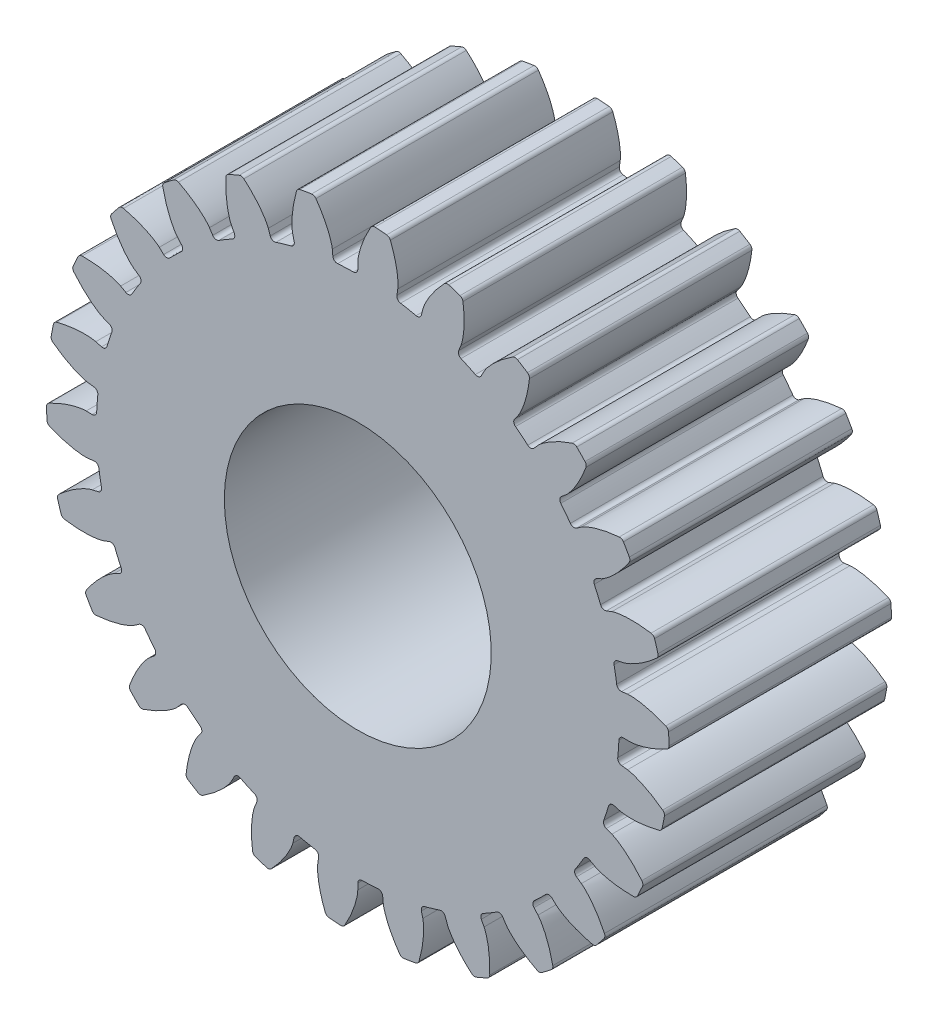
SolidWorks part; units mm, degrees
ref_plane "Front Plane" through (0, 0, 0) normal (0, 0, 1) x (1, 0, 0)
ref_plane "Top Plane" through (0, 0, 0) normal (0, 1, 0) x (1, 0, 0)
ref_plane "Right Plane" through (0, 0, 0) normal (1, 0, 0) x (0, 0, -1)
sketch "Involute Geometry" plane through (0, 0, 0) normal (0, 0, 1) x (1, 0, 0)
  line L0 (0, 12.216) -> (0, 0) construction
  line L1 (0, 0) -> (1.0333, 13.9618) construction
  line L2 (1.7984, 12.0829) -> (0, 0) construction
  line L3 (0.175, 12.9988) -> (0, 0) construction
  line L4 (0, 0) -> (1.7406, 12.883) construction
  circle A1 centre (0, 0) radius 12.216 construction
  circle A2 centre (0, 0) radius 13 construction
  circle A3 centre (0, 0) radius 14 construction
  circle A4 centre (0, 0) radius 11.75 construction
  arc A5 (0.6454, 13.9851) -> (1.4204, 13.9278) centre (0, 0) cw
  arc A6 (0.175, 12.9988) -> (1.7406, 12.883) centre (0, 0) cw construction
  spline S0 degree 4 poles (0, 12.216) (0, 12.2259) (0.0007, 12.2537) (0.0046, 12.3061) (0.0149, 12.3914) (0.0336, 12.4994) (0.064, 12.638) (0.108, 12.7997) (0.1647, 12.9755) (0.2354, 13.1642) (0.3138, 13.35) (0.3992, 13.5328) (0.4907, 13.7124) (0.6089, 13.9268) (0.7611, 14.1794) (0.9535, 14.4672) (1.1888, 14.7846) (1.4461, 15.0973) (1.7136, 15.3959) (1.9994, 15.6864) (2.287, 15.9594) (2.6008, 16.2305) (2.8982, 16.4744) (3.2472, 16.733) (3.5335, 16.9374) (3.9271, 17.1908) (4.1642, 17.3355) (4.4469, 17.4991) (4.5752, 17.5686) (4.654, 17.6115) knots 0 0 0 0 0 0.005377 0.015084 0.028532 0.04661 0.064855 0.092111 0.119476 0.146842 0.174209 0.201575 0.228941 0.256307 0.307035 0.361767 0.4165 0.471232 0.525964 0.580697 0.635429 0.690161 0.744894 0.799626 0.854358 0.909091 0.954545 1 1 1 1 1 construction
  spline S1 degree 4 poles (0, 12.216) (0, 12.2259) (0.0007, 12.2537) (0.0046, 12.3061) (0.0149, 12.3914) (0.0336, 12.4994) (0.064, 12.638) (0.108, 12.7997) (0.1647, 12.9755) (0.2354, 13.1642) (0.3138, 13.35) (0.3992, 13.5328) (0.4907, 13.7124) (0.6089, 13.9268) (0.7611, 14.1794) (0.9535, 14.4672) (1.1888, 14.7846) (1.4461, 15.0973) (1.7136, 15.3959) (1.9994, 15.6864) (2.287, 15.9594) (2.6008, 16.2305) (2.8982, 16.4744) (3.2472, 16.733) (3.5335, 16.9374) (3.8418, 17.1359) (3.9936, 17.2306) (4.0719, 17.2782) knots 0 0 0 0 0 0.005377 0.015084 0.028532 0.04661 0.064855 0.092111 0.119476 0.146842 0.174209 0.201575 0.228941 0.256307 0.307035 0.361767 0.4165 0.471232 0.525964 0.580697 0.635429 0.690161 0.744894 0.799626 0.854358 0.909091 0.909091 0.909091 0.909091 0.909091
  spline S3 degree 4 poles (1.7984, 12.0829) (1.7999, 12.0927) (1.8033, 12.1203) (1.8071, 12.1727) (1.8095, 12.2586) (1.8069, 12.3682) (1.7972, 12.5097) (1.7775, 12.6762) (1.7473, 12.8584) (1.7051, 13.0554) (1.655, 13.2507) (1.5974, 13.4441) (1.5334, 13.6352) (1.448, 13.8647) (1.3347, 14.1369) (1.1867, 14.45) (1.0007, 14.7985) (0.7922, 15.1457) (0.5716, 15.4804) (0.3317, 15.8098) (0.0874, 16.1222) (-0.1831, 16.4365) (-0.4413, 16.7215) (-0.7484, 17.0287) (-1.0015, 17.2731) (-1.3535, 17.5817) (-1.5667, 17.7597) (-1.8223, 17.9631) (-1.9389, 18.0507) (-2.0106, 18.1047) knots 0 0 0 0 0 0.005377 0.015084 0.028532 0.04661 0.064855 0.092111 0.119476 0.146842 0.174209 0.201575 0.228941 0.256307 0.307035 0.361767 0.4165 0.471232 0.525964 0.580697 0.635429 0.690161 0.744894 0.799626 0.854358 0.909091 0.954545 1 1 1 1 1 construction
  spline S4 degree 4 poles (1.7984, 12.0829) (1.7999, 12.0927) (1.8033, 12.1203) (1.8071, 12.1727) (1.8095, 12.2586) (1.8069, 12.3682) (1.7972, 12.5097) (1.7775, 12.6762) (1.7473, 12.8584) (1.7051, 13.0554) (1.655, 13.2507) (1.5974, 13.4441) (1.5334, 13.6352) (1.448, 13.8647) (1.3347, 14.1369) (1.1867, 14.45) (1.0007, 14.7985) (0.7922, 15.1457) (0.5716, 15.4804) (0.3317, 15.8098) (0.0874, 16.1222) (-0.1831, 16.4365) (-0.4413, 16.7215) (-0.7484, 17.0287) (-1.0015, 17.2731) (-1.2772, 17.5148) (-1.4134, 17.6308) (-1.4839, 17.6894) knots 0 0 0 0 0 0.005377 0.015084 0.028532 0.04661 0.064855 0.092111 0.119476 0.146842 0.174209 0.201575 0.228941 0.256307 0.307035 0.361767 0.4165 0.471232 0.525964 0.580697 0.635429 0.690161 0.744894 0.799626 0.854358 0.909091 0.909091 0.909091 0.909091 0.909091
  dimension "D5" = 6.923
sketch "Sketch2" plane through (0, 0, 0) normal (0, 0, 1) x (1, 0, 0)
  circle A0 centre (0, 0) radius 11.75 construction
  circle A1 centre (0, 0) radius 11.75
extrude "Boss-Extrude1" add sketch "Sketch2" along normal mid plane 10
sketch "Sketch3" plane through (0, 0, 0) normal (0, 0, 1) x (1, 0, 0)
  line L0 (0, 12.216) -> (0, 0) construction
  line L1 (1.7984, 12.0829) -> (0, 0) construction
  line L2 (0, 12.216) -> (0, 11.75)
  line L4 (1.7984, 12.0829) -> (1.7298, 11.622)
  circle A1 centre (0, 0) radius 11.75 construction
  arc A3 (0, 11.75) -> (1.7298, 11.622) centre (0, 0) cw
  arc A4 (1.4204, 13.9278) -> (0.6454, 13.9851) centre (0, 0) ccw construction
  arc A5 (1.4204, 13.9278) -> (0.6454, 13.9851) centre (0, 0) ccw
  spline S0 degree 4 poles (999.8581, 25.2356) (18.0155, 10.2173) (0.3577, 10.7107) (-0.0848, 11.5636) (0.0149, 12.3914) (0.0336, 12.4994) (0.064, 12.638) (0.108, 12.7997) (0.1647, 12.9755) (0.2354, 13.1642) (0.3138, 13.35) (0.3992, 13.5328) (0.4907, 13.7124) (0.6089, 13.9268) (0.7611, 14.1794) (0.9535, 14.4672) (1.1888, 14.7846) (1.4461, 15.0973) (1.7136, 15.3959) (1.9994, 15.6864) (2.287, 15.9594) (2.6008, 16.2305) (2.8982, 16.4744) (3.2472, 16.733) (4.4419, 17.5861) (8.1221, 19.6216) (-23.9178, -0.2396) (859.2438, 535.5339) knots -0.405932 -0.405932 -0.405932 -0.405932 -0.405932 0.005377 0.015084 0.028532 0.04661 0.064855 0.092111 0.119476 0.146842 0.174209 0.201575 0.228941 0.256307 0.307035 0.361767 0.4165 0.471232 0.525964 0.580697 0.635429 0.690161 0.744894 0.799626 0.854358 1.603617 1.603617 1.603617 1.603617 1.603617 only from (0, 12.216) to (3.8711, 11.595) construction
  spline S1 degree 4 poles (0, 12.216) (0, 12.2259) (0.0007, 12.2537) (0.0046, 12.3061) (0.0149, 12.3914) (0.0336, 12.4994) (0.064, 12.638) (0.108, 12.7997) (0.1647, 12.9755) (0.2354, 13.1642) (0.3138, 13.35) (0.3992, 13.5328) (0.4919, 13.7149) (0.5664, 13.8498) (0.6183, 13.9394) (0.6454, 13.9851) knots 0 0 0 0 0 0.005377 0.015084 0.028532 0.04661 0.064855 0.092111 0.119476 0.146842 0.174209 0.201575 0.228941 0.257808 0.257808 0.257808 0.257808 0.257808
  spline S3 degree 4 poles (-985.2487, 172.157) (-16.315, 12.7581) (1.223, 10.6467) (1.7863, 11.4251) (1.8095, 12.2586) (1.8069, 12.3682) (1.7972, 12.5097) (1.7775, 12.6762) (1.7473, 12.8584) (1.7051, 13.0554) (1.655, 13.2507) (1.5974, 13.4441) (1.5334, 13.6352) (1.448, 13.8647) (1.3347, 14.1369) (1.1867, 14.45) (1.0007, 14.7985) (0.7922, 15.1457) (0.5716, 15.4804) (0.3317, 15.8098) (0.0874, 16.1222) (-0.1831, 16.4365) (-0.4413, 16.7215) (-0.7484, 17.0287) (-1.8045, 18.0484) (-5.1449, 20.6035) (23.6219, -3.7581) (-771.0418, 656.1943) knots -0.405932 -0.405932 -0.405932 -0.405932 -0.405932 0.005377 0.015084 0.028532 0.04661 0.064855 0.092111 0.119476 0.146842 0.174209 0.201575 0.228941 0.256307 0.307035 0.361767 0.4165 0.471232 0.525964 0.580697 0.635429 0.690161 0.744894 0.799626 0.854358 1.603617 1.603617 1.603617 1.603617 1.603617 only from (1.7984, 12.0829) to (-1.4839, 17.6894) construction
  spline S4 degree 4 poles (1.7984, 12.0829) (1.7999, 12.0927) (1.8033, 12.1203) (1.8071, 12.1727) (1.8095, 12.2586) (1.8069, 12.3682) (1.7972, 12.5097) (1.7775, 12.6762) (1.7473, 12.8584) (1.7051, 13.0554) (1.655, 13.2507) (1.5974, 13.4441) (1.5325, 13.6379) (1.4787, 13.7823) (1.4405, 13.8785) (1.4204, 13.9278) knots 0 0 0 0 0 0.005377 0.015084 0.028532 0.04661 0.064855 0.092111 0.119476 0.146842 0.174209 0.201575 0.228941 0.257808 0.257808 0.257808 0.257808 0.257808
extrude "Boss-Extrude2" add sketch "Sketch3" along normal through all and the other way through all
fillet "Fillet2" [suppressed] radius 0.381
pattern_circular "CirPattern1" count 26 over 360 about axis through (0, 0, 5) along (0, 0, -1) of "Boss-Extrude2", "Fillet2"
ref_axis "Axis1" through (0, 0, 5) along (0, 0, -1)
sketch "Sketch4" plane through (0, 0, -5) normal (0, 0, -1) x (-1, 0, 0)
  circle A1 centre (0, 0) radius 6
  dimension "D1" = 12
extrude "Cut-Extrude1" cut sketch "Sketch4" against normal through all
fillet "Fillet3" radius 0.2 104 edges at (-8.5821, 8.0256, 0) (-9.6701, 6.6748, 0) (-10.9864, 4.1666, 0) (-11.3287, 3.1181, 0) (-11.6643, 1.4163, 0) (-11.7457, 0.3163, 0) (-11.6643, -1.4163, 0) (-11.4801, -2.5038, 0) (-10.9864, -4.1666, 0) (-10.5473, -5.1784, 0) (-9.6701, -6.6748, 0) (-9.0016, -7.5521, 0) (-7.7917, -8.795, 0) (-6.9327, -9.4869, 0) (-5.4605, -10.4041, 0) (-4.4609, -10.8703, 0) (-2.812, -11.4086, 0) (-1.7298, -11.622, 0) (0, -11.75, 0) (1.1018, -11.6982, 0) (2.812, -11.4086, 0) (3.8693, -11.0946, 0) (5.4605, -10.4041, 0) (6.412, -9.8462, 0) (7.7917, -8.795, 0) (8.5821, -8.0256, 0) (9.6701, -6.6748, 0) (10.2533, -5.7386, 0) (10.9864, -4.1666, 0) (11.3287, -3.1181, 0) (11.6643, -1.4163, 0) (11.7457, -0.3163, 0) (11.6643, 1.4163, 0) (11.4801, 2.5038, 0) (10.9864, 4.1666, 0) (10.5473, 5.1784, 0) (9.6701, 6.6748, 0) (9.0016, 7.5521, 0) (7.7917, 8.795, 0) (6.9327, 9.4869, 0) (5.4605, 10.4041, 0) (4.4609, 10.8703, 0) (2.812, 11.4086, 0) (1.7298, 11.622, 0) (0, 11.75, 0) (-10.2533, 5.7386, 0) (-1.1018, 11.6982, 0) (-2.812, 11.4086, 0) (-3.8693, 11.0946, 0) (-5.4605, 10.4041, 0) (-6.412, 9.8462, 0) (-7.7917, 8.795, 0) (1.4204, 13.9278, 0) (3.9735, 13.4243, 0) (4.7123, 13.1831, 0) (7.0707, 12.0833, 0) (7.7303, 11.6723, 0) (9.757, 10.04, 0) (10.299, 9.4831, 0) (11.8762, 7.4133, 0) (12.2692, 6.7429, 0) (13.3052, 4.3557, 0) (13.5264, 3.6107, 0) (13.9609, 1.045, 0) (13.9974, 0.2687, 0) (13.8053, -2.3265, 0) (13.655, -3.0889, 0) (12.8474, -5.5627, 0) (12.519, -6.267, 0) (11.1429, -8.4756, 0) (10.6554, -9.0809, 0) (8.7907, -10.896, 0) (8.1726, -11.367, 0) (5.9277, -12.6832, 0) (5.2148, -12.9925, 0) (2.7202, -13.7332, 0) (1.954, -13.863, 0) (-0.6454, -13.9851, 0) (-1.4204, -13.9278, 0) (-3.9735, -13.4243, 0) (-4.7123, -13.1831, 0) (-7.0707, -12.0833, 0) (-7.7303, -11.6723, 0) (-9.757, -10.04, 0) (-10.299, -9.4831, 0) (-11.8762, -7.4133, 0) (-12.2692, -6.7429, 0) (-13.3052, -4.3557, 0) (-13.5264, -3.6107, 0) (-13.9609, -1.045, 0) (-13.9974, -0.2687, 0) (-13.8053, 2.3265, 0) (-13.655, 3.0889, 0) (-12.8474, 5.5627, 0) (-12.519, 6.267, 0) (-11.1429, 8.4756, 0) (-10.6554, 9.0809, 0) (-8.7907, 10.896, 0) (-8.1726, 11.367, 0) (-5.9277, 12.6832, 0) (-5.2148, 12.9925, 0) (-2.7202, 13.7332, 0) (-1.954, 13.863, 0) (0.6454, 13.9851, 0)
equation "\"N\" = 26'Number of Teeth"
equation "\"m\" = 1mm'Diametral Pitch"
equation "\"phi\"= 20deg'Pressure Angle"
equation "\"a\"= \"m\"'Addendum"
equation "\"b\"= 1.25 * \"m\"'Dedendum"
equation "\"Dp\"= \"N\" * \"m\"'Pitch diameter"
equation "\"Db\"= \"Dp\" * cos ( \"phi\" )'Base diameter"
equation "\"D1@Involute Geometry\" = \"Db\""
equation "\"D2@Involute Geometry\" = \"Dp\""
equation "\"D3@Involute Geometry\" = \"Dp\" + 2 * \"a\""
equation "\"D4@Involute Geometry\" = \"Dp\" - 2 * \"b\""
equation "\"D1@CirPattern1\"=\"N\""
equation "\"D5@Involute Geometry\"=180/\"N\""
equation "\"D1@Boss-Extrude1\"=10*\"m\""
equation "\"alpha\"= sqr ( \"Dp\" ^ 2 - \"Db\" ^ 2 ) / \"Db\" * 180 / pi - \"phi\""
equation "\"beta\"= ( ( 360deg / \"N\" ) / 4 - \"alpha\" )"
